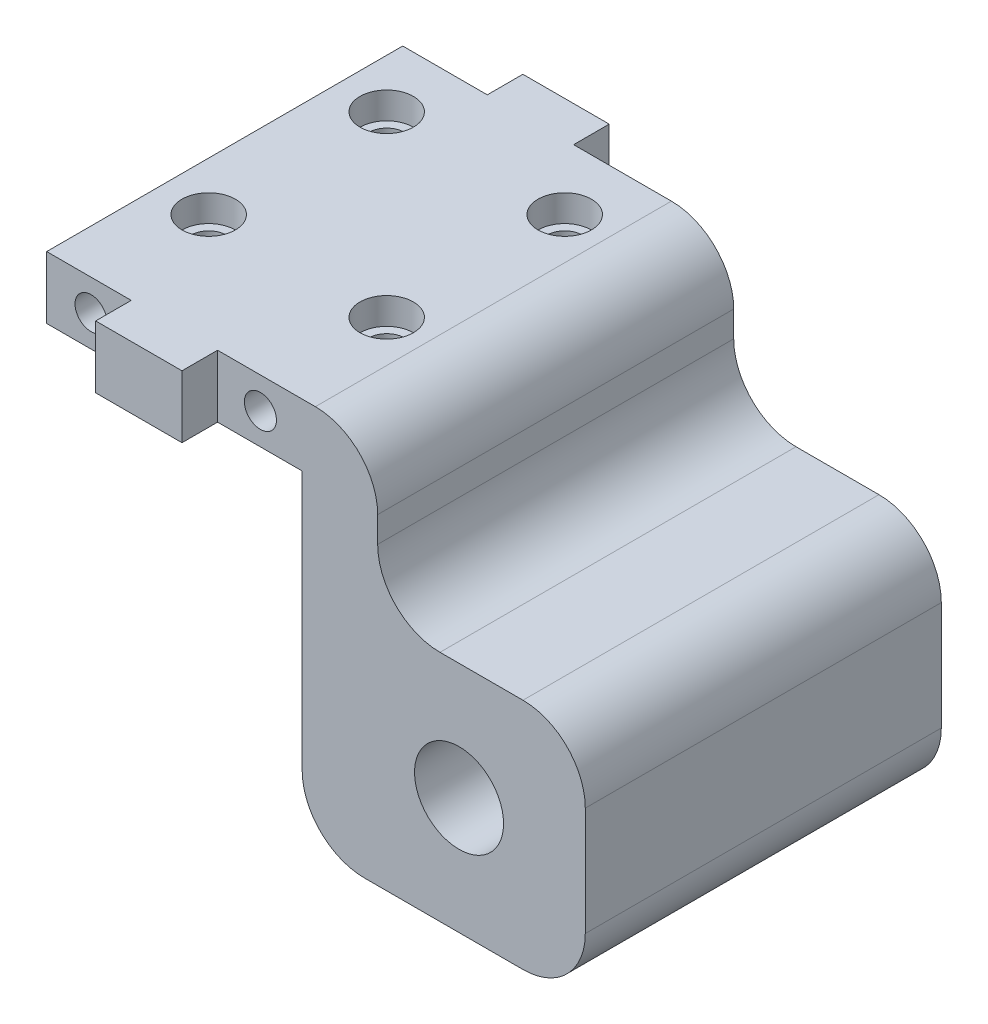
SolidWorks part; units mm, degrees
ref_plane "Front Plane" through (0, 0, 0) normal (0, 0, 1) x (1, 0, 0)
ref_plane "Top Plane" through (0, 0, 0) normal (0, 1, 0) x (1, 0, 0)
ref_plane "Right Plane" through (0, 0, 0) normal (1, 0, 0) x (0, 0, -1)
sketch "Sketch1" plane through (0, 0, 0) normal (0, 0, 1) x (1, 0, 0)
  line L2 (-10.8436, 3.5) -> (-10.8436, -3.5)
  line L3 (-10.8436, -3.5) -> (15.8563, -3.5)
  line L5 (24.3429, 3.5) -> (24.3429, -13.3983)
  line L6 (24.3429, -13.3983) -> (47.6667, -13.3983)
  line L9 (47.6667, -39.6017) -> (15.8563, -39.6017)
  line L10 (15.8563, -39.6017) -> (15.8563, -3.5)
  line L11 (-10.8436, 3.5) -> (24.3429, 3.5)
  line L12 (47.6667, -13.3983) -> (47.6667, -39.6017)
  line L13 (15.8563, -5.1) -> (15.8563, -12.9) construction
  line L14 (-10.2436, -3.5) -> (-3.7437, -3.5) construction
  line L15 (-10.8436, -8.7) -> (-10.8436, -4.1) construction
  point P1 (0, 0)
  point P7 (47.6667, -26.5)
  dimension "D1" = 7
extrude "Boss-Extrude1" add sketch "Sketch1" along normal blind 40
sketch "Sketch2" plane through (0, 0, 40) normal (0, 0, 1) x (1, 0, 0)
  circle A0 centre (33.484, -26.5) radius 10.8
  circle A1 centre (33.484, -26.5) radius 5
  dimension "D1" = 10
extrude "Cut-Extrude1" cut sketch "Sketch2" along normal blind 5 from surface contours A1 | A0 A1 region at (22.9895, -26.5, 40) region at (33.484, -26.5, 40) starting at face at (19.2556, -13.25, 0)
extrude "Cut-Extrude2" cut sketch "Sketch2<3>" against normal through all contours A1 region at (33.484, -26.5, 40)
sketch "Sketch2<3>" plane through (0, 0, 40) normal (0, 0, 1) x (1, 0, 0) same geometry as "Sketch2"
sketch "Sketch3" plane through (0, 0, 40) normal (0, 0, 1) x (1, 0, 0)
  circle A0 centre (33.6086, -34.499) radius 2
  circle A1 centre (25.485, -26.6246) radius 2
  circle A2 centre (33.3594, -18.501) radius 2
  circle A3 centre (41.483, -26.3754) radius 2
  dimension "D1" = 4
extrude "Cut-Extrude3" cut sketch "Sketch3" along normal blind 15 from surface starting at face at (22.684, -26.5, 0)
sketch "Sketch5" plane through (0, -3.5, 0) normal (0, -1, 0) x (1, 0, 0)
  circle A0 centre (-7.3436, 7.3) radius 2
  circle A1 centre (12.6564, 7.3) radius 2
  circle A3 centre (-7.3436, 27.3) radius 2
  circle A4 centre (12.6564, 27.3) radius 2
  dimension "D1" = 4
extrude "Cut-Extrude4" cut sketch "Sketch5" against normal through all
fillet "Fillet1" radius 7 5 edges at (47.6667, -39.6017, 20) (15.8563, -39.6017, 20) (24.3429, 3.5, 20) (24.3429, -13.3983, 20) (47.6667, -13.3983, 20)
sketch "Sketch12" plane through (0, 0, 0) normal (0, 0, -1) x (-1, 0, 0)
  circle A0 centre (-11.17, 0) radius 1.75
  circle A1 centre (7.8617, 0) radius 1.75
  dimension "D1" = 3.5
extrude "Cut-Extrude11" cut sketch "Sketch12" against normal blind 4
sketch "Sketch14" plane through (0, 3.5, 0) normal (0, 1, 0) x (1, 0, 0)
  circle A0 centre (-7.3436, -7.3) radius 3
  circle A1 centre (-7.3436, -27.3) radius 3
  circle A2 centre (12.6564, -27.3) radius 3
  circle A3 centre (12.6564, -7.3) radius 3
  dimension "D1" = 6
extrude "Cut-Extrude12" cut sketch "Sketch14" against normal blind 3
sketch "Sketch15" plane through (0, 0, 40) normal (0, 0, 1) x (1, 0, 0)
  circle A0 centre (-7.8617, 0) radius 1.8
  circle A1 centre (11.17, 0) radius 1.8
  point P6 (0, 0)
  point P7 (11.17, 0)
  point P9 (-7.7872, -0.3552)
  point P10 (-7.8617, 0)
  dimension "D1" = 3.6
extrude "Cut-Extrude13" cut sketch "Sketch15" against normal blind 9
sketch "Sketch16" plane through (-10.8436, 0, 0) normal (-1, 0, 0) x (0, 0, 1)
  line L4 (0, 3.5) -> (0, -3.5)
  line L5 (0, -3.5) -> (40, -3.5)
  line L6 (40, -3.5) -> (40, 3.5)
  line L7 (40, 3.5) -> (0, 3.5)
  line L8 (0, 3.5) -> (0, -3.5)
  line L9 (0, -3.5) -> (40, -3.5)
  line L10 (40, -3.5) -> (40, 3.5)
  line L11 (40, 3.5) -> (0, 3.5)
  dimension "D1" = 0
extrude "Boss-Extrude5" add sketch "Sketch16" along normal blind 2
sketch "Sketch18" plane through (0, 0, 0) normal (0, 0, -1) x (-1, 0, 0)
  line L0 (-17.3429, 3.5) -> (12.8436, 3.5) construction
  line L1 (-6.3564, 3.5) -> (3.3436, 3.5)
  line L2 (-6.3564, 3.5) -> (-6.3564, -3.5)
  line L3 (-6.3564, -3.5) -> (3.3436, -3.5)
  line L4 (3.3436, 3.5) -> (3.3436, -3.5)
  line L5 (12.8436, -3.5) -> (-15.8563, -3.5) construction
  point P12 (-1.5064, -3.5)
  point P13 (-1.5064, -3.5)
  dimension "D1" = 9.7
  dimension "D2" = 0
extrude "Boss-Extrude6" add sketch "Sketch18" along normal blind 4
ref_plane "Plane2" through (0, 0, 20) normal (0, 0, -1) x (-1, 0, 0)
mirror "Mirror6" about plane through (0, 0, 20) normal (0, 0, -1) of "Boss-Extrude6"
